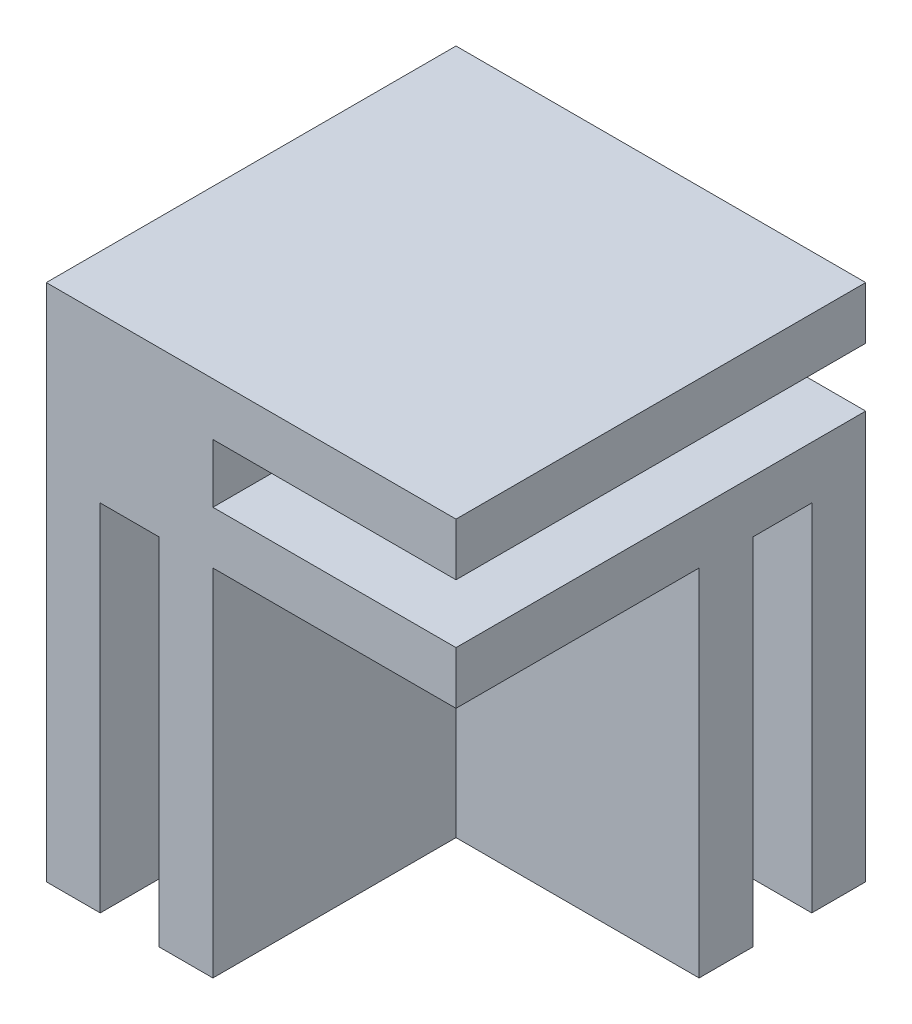
SolidWorks part; units mm, degrees
ref_plane "Plan de face" through (0, 0, 0) normal (0, 0, 1) x (1, 0, 0)
ref_plane "Plan de dessus" through (0, 0, 0) normal (0, 1, 0) x (1, 0, 0)
ref_plane "Plan de droite" through (0, 0, 0) normal (1, 0, 0) x (0, 0, -1)
sketch "Esquisse1" plane through (0, 0, 0) normal (0, 1, 0) x (1, 0, 0)
  line L1 (-35.8867, 13.5315) -> (-5.8867, 13.5315)
  line L2 (-35.8867, 13.5315) -> (-35.8867, -16.4685)
  line L3 (-35.8867, -16.4685) -> (-5.8867, -16.4685)
  line L4 (-5.8867, 13.5315) -> (-5.8867, -16.4685)
  dimension "D1" = 30
  dimension "D2" = 30
extrude "Boss.-Extru.1" add sketch "Esquisse1" along normal blind 38
sketch "Esquisse2" plane through (0, 0, 0) normal (0, -1, 0) x (1, 0, 0)
  line L0 (-5.8867, 16.4685) -> (-5.8867, -13.5315) construction
  line L1 (-5.8867, -9.5815) -> (-23.6867, -9.5815)
  line L2 (-5.8867, -9.5815) -> (-5.8867, -5.2815)
  line L3 (-5.8867, -5.2815) -> (-23.6867, -5.2815)
  line L4 (-23.6867, -9.5815) -> (-23.6867, -5.2815)
  line L5 (-35.8867, 16.4685) -> (-5.8867, 16.4685) construction
  line L6 (-27.6367, 16.4685) -> (-31.9367, 16.4685)
  line L7 (-27.6367, 16.4685) -> (-27.6367, -1.3315)
  line L8 (-27.6367, -1.3315) -> (-31.9367, -1.3315)
  line L9 (-31.9367, 16.4685) -> (-31.9367, -1.3315)
  line L15 (-35.8867, -13.5315) -> (-35.8867, 16.4685) construction
  line L16 (-5.8867, -13.5315) -> (-35.8867, -13.5315) construction
  line L18 (-5.8867, 16.4685) -> (-23.6867, 16.4685)
  line L19 (-5.8867, 16.4685) -> (-5.8867, -1.3315)
  line L20 (-5.8867, -1.3315) -> (-23.6867, -1.3315)
  line L21 (-23.6867, 16.4685) -> (-23.6867, -1.3315)
  dimension "D1" = 4.3
  dimension "D2" = 17.8
  dimension "D3" = 3.95
  dimension "D4" = 4.3
  dimension "D5" = 17.8
  dimension "D6" = 3.95
extrude "Enlèv. mat.-Extru.1" cut sketch "Esquisse2" against normal blind 26
sketch "Esquisse3" plane through (0, 0, 16.4685) normal (0, 0, 1) x (1, 0, 0)
  line L0 (-5.8867, 38) -> (-5.8867, 26) construction
  line L1 (-23.6867, 34.15) -> (-5.8867, 34.15)
  line L2 (-23.6867, 34.15) -> (-23.6867, 29.85)
  line L3 (-23.6867, 29.85) -> (-5.8867, 29.85)
  line L4 (-5.8867, 34.15) -> (-5.8867, 29.85)
  line L6 (-35.8867, 38) -> (-5.8867, 38) construction
  dimension "D1" = 4.3
  dimension "D2" = 17.8
  dimension "D3" = 3.85
extrude "Enlèv. mat.-Extru.3" cut sketch "Esquisse3" against normal through all
